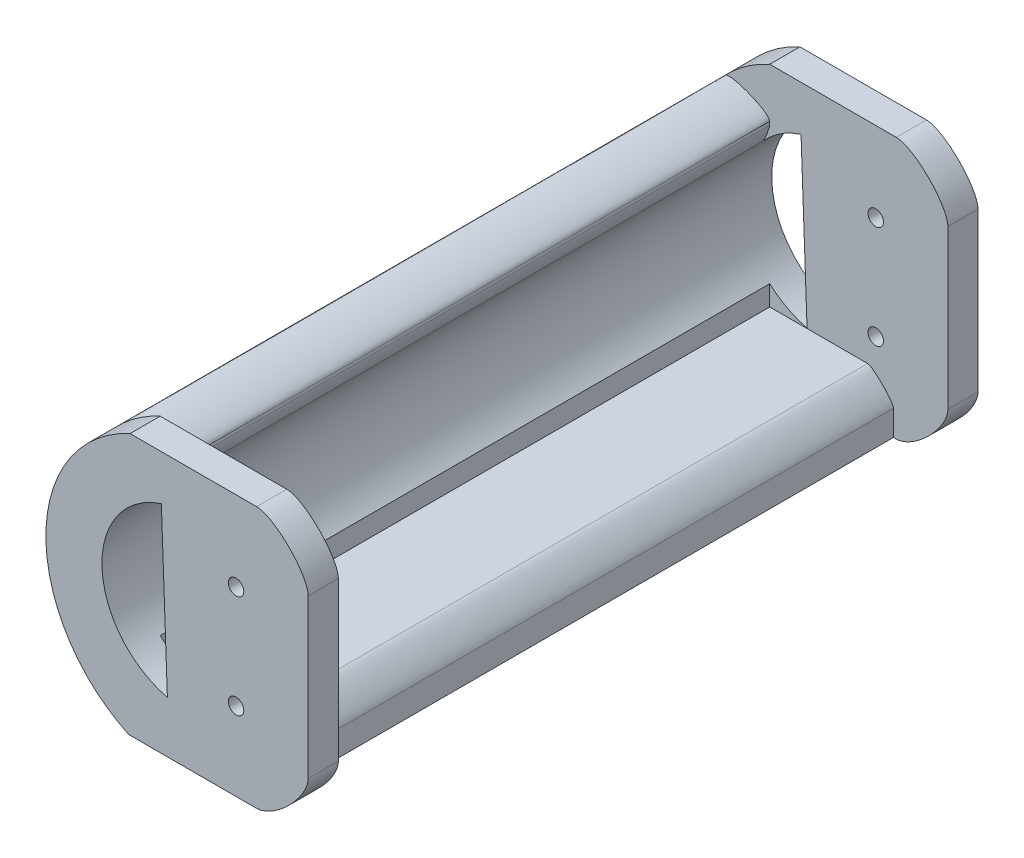
SolidWorks part; units mm, degrees
ref_plane "Front Plane" through (0, 0, 0) normal (0, 0, 1) x (1, 0, 0)
ref_plane "Top Plane" through (0, 0, 0) normal (0, 1, 0) x (1, 0, 0)
ref_plane "Right Plane" through (0, 0, 0) normal (1, 0, 0) x (0, 0, -1)
sketch "Sketch1" plane through (0, 0, 0) normal (0, 0, 1) x (1, 0, 0)
  line L1 (50, -24.9474) -> (-207.728, -24.9474)
  line L3 (-213.0381, 15.4715) -> (-219.1138, 15.4715)
  line L5 (-184.5427, -25.2474) -> (-184.5427, -35.2474)
  line L6 (-184.5427, -35.2474) -> (-219.3707, -35.2474)
  line L7 (-184.5427, -25.2474) -> (-211.8721, -25.2474)
  line L8 (-224.5666, -9.7018) -> (-224.5666, -2.8871) construction
  line L9 (-224.5666, -2.8871) -> (-224.5666, -22.9457) construction
  line L11 (-213.0381, 15.4715) -> (-184.5427, 15.4715)
  line L12 (-184.5427, 15.4715) -> (-184.5427, 6.7272)
  line L13 (-184.5427, 6.7272) -> (-213.0381, 6.7272)
  arc A2 (-211.8721, -25.2474) -> (-213.0381, 6.7272) centre (-207.9591, -9.0962) cw
  arc A3 (-219.1138, 15.4715) -> (-219.3707, -35.2474) centre (-207.5049, -9.9474) ccw
  dimension "D4" = 0.3
  dimension "D8" = 10
extrude "Boss-Extrude1" add sketch "Sketch1" along normal blind 130 contours A3 L6 L5 L7 A2 L13 L12 L11 L3
sketch "Sketch6" plane through (0, -25.2474, 0) normal (0, 1, 0) x (1, 0, 0)
  line L1 (-184.2857, -5.85) -> (-219.1138, -5.85)
  line L2 (-184.2857, -5.85) -> (-184.2324, -124.15)
  line L3 (-184.2324, -124.15) -> (-219.1138, -124.15)
  line L4 (-219.1138, -5.85) -> (-219.1138, -124.15)
  line L5 (-211.8721, -130) -> (-211.8721, 0) construction
  line L6 (-219.1138, -130) -> (-219.1138, 0) construction
  point P6 (-211.8721, -65)
  point P7 (-219.1138, -65)
  dimension "D1" = 118.3
  dimension "D2" = 34.828
extrude "Cut-Extrude3" cut sketch "Sketch6" against normal through all both and the other way through all
loft "Loft4" add section face at (-198.2074, -25.2474, 127.075) section face at (-198.7904, 6.7272, 127.075)
loft "Loft5" add section face at (-198.2074, -25.2474, 2.925) section face at (-198.7904, 6.7272, 2.925)
fillet "Fillet2" radius 10 3 edges at (-184.5427, -35.2474, 2.925) (-184.5427, 15.4715, 127.075) (-184.5427, -35.2474, 127.075)
sketch "Sketch8" plane through (0, 0, 130) normal (0, 0, 1) x (1, 0, 0)
  line L0 (-184.5427, 5.4715) -> (-184.5427, -25.2474) construction
  line L4 (-194.5427, 15.4715) -> (-219.1138, 15.4715) construction
  circle A0 centre (-198.5427, -0.0285) radius 1.5
  circle A1 centre (-198.5427, -20.0285) radius 1.5
  dimension "D2" = 3
  dimension "D3" = 3
  dimension "D1" = 20
  dimension "D4" = 14
  dimension "D5" = 15.5
extrude "Cut-Extrude4" cut sketch "Sketch8" against normal through all both and the other way through all
sketch "Sketch9" plane through (0, 0, 130) normal (0, 0, 1) x (1, 0, 0)
  line L1 (-219.3707, -35.2474) -> (-195.0973, -35.2474)
  line L2 (-219.3707, -35.2474) -> (-219.3707, -25.3285)
  line L3 (-219.3707, -25.3285) -> (-195.0973, -25.3285)
  line L4 (-195.0973, -35.2474) -> (-195.0973, -25.3285)
  circle A1 centre (-198.5427, -20.0285) radius 1.5 construction
  dimension "D1" = 5.3
extrude "Boss-Extrude5" add sketch "Sketch9" against normal blind 129
fillet "Fillet5" radius 5 3 edges at (-219.1138, 3.2224, 65) (-195.0973, -25.3285, 65) (-219.1138, 15.4715, 65)
